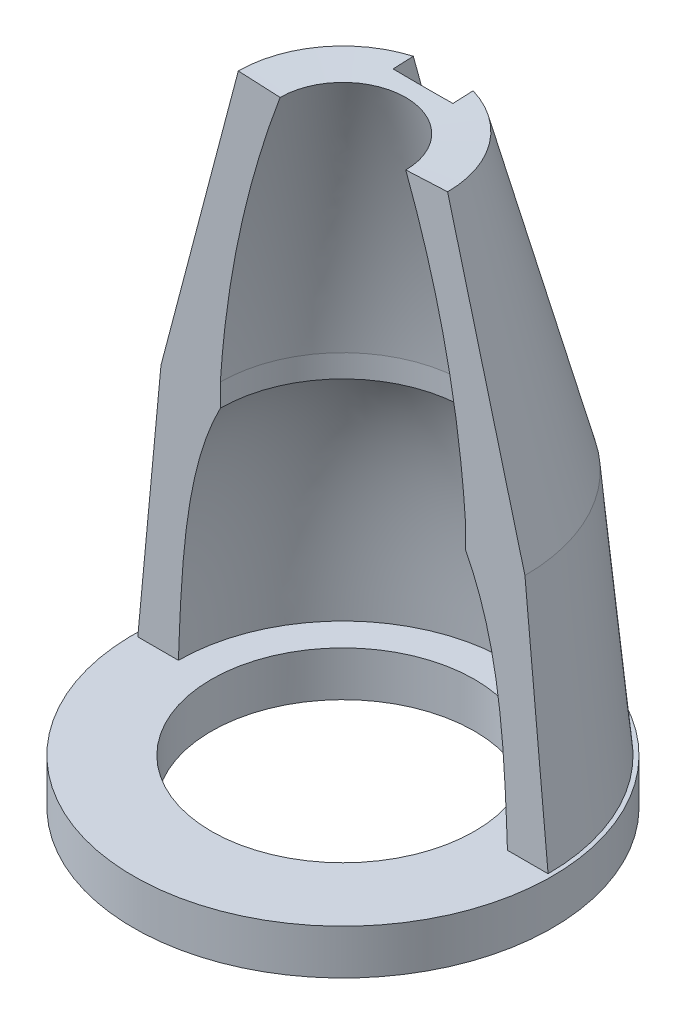
SolidWorks part; units mm, degrees
ref_plane "Alzado" through (0, 0, 0) normal (0, 0, 1) x (1, 0, 0)
ref_plane "Planta" through (0, 0, 0) normal (0, 1, 0) x (1, 0, 0)
ref_plane "Vista lateral" through (0, 0, 0) normal (1, 0, 0) x (0, 0, -1)
sketch "Croquis1" plane through (0, 0, 0) normal (0, 0, 1) x (1, 0, 0)
  line L0 (0, 0) -> (0, 1.5)
  line L1 (0, 1.5) -> (5.5, 1.5)
  line L4 (0, 1.5) -> (0, 21.6741) construction
  line L5 (0, 0) -> (7, 0)
  line L6 (7, 0) -> (6.0844, 9.7493)
  line L7 (6.0844, 9.7493) -> (3.4984, 19.566)
  line L8 (2.1, 19.5) -> (3.4984, 19.566)
  line L10 (4.1, 9.5) -> (4.1, 10.259)
  spline S0 degree 3 poles (4.1, 9.5) (5.2889, 7.2001) (5.3946, 4.3048) (5.5, 1.5) knots 0 0 0 0 0.667768 0.667768 0.667768 0.667768
  spline S1 degree 2 poles (2.1, 19.5) (3.7859, 15.0303) (4.1, 10.259) knots 0 0 0 1 1 1
  dimension "D1" = 5.5
  dimension "D2" = 7
  dimension "D3" = 2
  dimension "D4" = 2.1
  dimension "D5" = 1.4
  dimension "D8" = 1.5
  dimension "D9" = 4.1
revolve "Revolución1" add sketch "Croquis1" angle 180 about L4
sketch "Croquis2" plane through (0, 0, 0) normal (0, -1, 0) x (1, 0, 0)
  circle A0 centre (0, 0) radius 7
extrude "Saliente-Extruir1" add sketch "Croquis2" against normal blind 1.5
sketch "Croquis3" plane through (0, 0, 0) normal (0, -1, 0) x (1, 0, 0)
  circle A0 centre (0, 0) radius 4.4
  dimension "D1" = 8.8
extrude "Cortar-Extruir1" cut sketch "Croquis3" against normal blind 3
sketch "Croquis4" plane through (0, 0, 0) normal (1, 0, 0) x (0, 0, -1)
  line L15 (6.7687, 7.141) -> (6.0687, 7.141)
  line L16 (6.0687, 7.141) -> (2.337, 20.7797)
  line L17 (2.337, 20.7797) -> (3.4984, 19.566)
  line L18 (3.4984, 19.566) -> (4.8987, 19.566)
  line L19 (4.8987, 19.566) -> (8.789, 7.141)
  line L20 (8.789, 7.141) -> (6.7687, 7.141)
  dimension "D1" = 0.7
  dimension "D2" = 0.8
ref_axis "Eje1" through (0, 1.5, 0) along (0, -1, 0)
extrude "Cortar-Extruir6" cut sketch "Croquis4" against normal blind 1 and the other way blind 1
